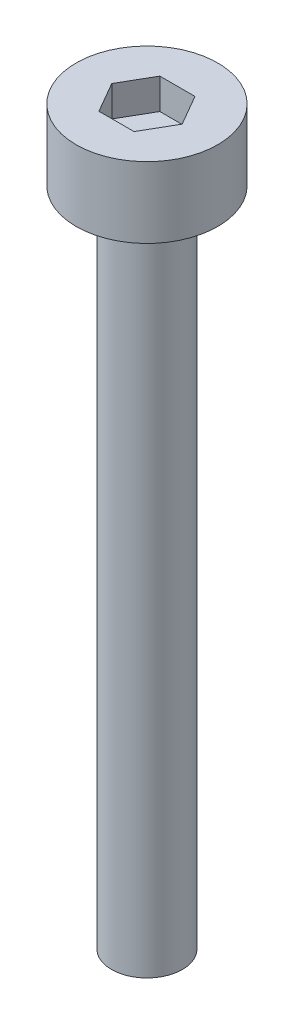
SolidWorks part; units mm, degrees
ref_plane "Front Plane" through (0, 0, 0) normal (0, 0, 1) x (1, 0, 0)
ref_plane "Top Plane" through (0, 0, 0) normal (0, 1, 0) x (1, 0, 0)
ref_plane "Right Plane" through (0, 0, 0) normal (1, 0, 0) x (0, 0, -1)
sketch "Sketch1" plane through (0, 0, 0) normal (0, 1, 0) x (1, 0, 0)
  circle A0 centre (0, 0) radius 1.5
  dimension "D1" = 3
extrude "ScrewShaft" add sketch "Sketch1" along normal blind 28
sketch "Sketch2" plane through (0, 28, 0) normal (0, 1, 0) x (1, 0, 0)
  circle A0 centre (0, 0) radius 3
  dimension "D1" = 6
extrude "Boss-Extrude2" add sketch "Sketch2" along normal blind 3
sketch "Sketch3" plane through (0, 31, 0) normal (0, 1, 0) x (1, 0, 0)
  line L0 (0, 0) -> (0, 1.29) construction
  line L1 (1.4896, 0) -> (0.7448, 1.29)
  line L2 (0.7448, 1.29) -> (-0.7448, 1.29)
  line L3 (-0.7448, 1.29) -> (-1.4896, 0)
  line L4 (-1.4896, 0) -> (-0.7448, -1.29)
  line L5 (-0.7448, -1.29) -> (0.7448, -1.29)
  line L6 (0.7448, -1.29) -> (1.4896, 0)
  circle A0 centre (0, 0) radius 1.29 construction
  dimension "D1" = 2.58
extrude "Cut-Extrude1" cut sketch "Sketch3" against normal blind 1.3
equation "\"X-ROD-SPACING\"=45"
equation "\"Y-ROD-SPACING\"=75"
equation "\"Z-ROD-SPACING\"=17.5"
equation "\"Y-BED-OFFSET\"=2"
equation "\"Y-BED-ROD-INSET\"=3.5"
equation "\"T-SLOT-NUT-FILLET-RADIUS\"=0.5"
equation "\"T-SLOT-SCREW-SHAFT-RADIUS\"=1.55"
equation "\"T-SLOT-SCREW-SHAFT-CUTOUT-LENGTH\"=11"
equation "\"T-SLOT-NUT-DEPTH\"=3.5"
equation "\"T-SLOT-NUT-WIDTH\"=2.85"
equation "\"T-SLOT-NUT-END-DISTANCE\"=8"
equation "\"ACRYLIC-THICKNESS\"=10"
equation "\"ACRYLIC-THICKNESS2\"=4.5"
equation "\"ACRYLIC-TAB-CUTOUT-SIZE\"=\"ACRYLIC-THICKNESS\"+\"ACRYLIC-TAB-TOLERANCE\"*2"
equation "\"ACRYLIC-TAB-WIDTH\"=\"ACRYLIC-THICKNESS\""
equation "\"ACRYLIC-M3-HOLE\"=2.9"
equation "\"SMOOTHROD-CAP-SCREW-DISTANCE\"=20"
equation "\"FRAME-WIDTH-INNER\"=370"
equation "\"NEMA17-HOLE-SPACING\"=31"
equation "\"NEMA17-CENTRAL-CUTOUT\"=22.5"
equation "\"Z-BRACKET-REACH\"=57"
equation "\"TOP-BRACKET-SPACING\"=40"
equation "\"SMOOTHROD-X-LENGTH\"=350"
equation "\"SMOOTHROD-Y-LENGTH\"=350"
equation "\"SMOOTHROD-Z-LENGTH\"=350"
equation "\"SMOOTHROD-TIGHTENING-HEADROOM\"=.25"
equation "\"LEADSCREW-Z-LENGTH\"=300"
equation "\"SCREW-LENGTH-FRAME\"=\"ACRYLIC-THICKNESS\" + 10"
equation "\"SCREW-HEAD-RADIUS\"=6"
equation "\"PRINTED-X-SMOOTHROD-DIAMETER\"=8.8"
equation "\"PRINTED-X-SMOOTHROD-CUTOUT\"=10"
equation "\"PRINTED-X-BASE-HEIGHT\"=10"
equation "\"PRINTED-LM8UU-CUTOUT-SIZE\"=15.5"
equation "\"PRINTED-LM8UU-CUTOUT-LENGTH\"=24.5"
equation "\"PRINTED-X-IDLER-HEIGHT\"=16"
equation "\"PSU-MOUNTING-WIDTH\"=50"
equation "\"PSU-MOUNTING-HEIGHT\"=150"
equation "\"D1@ScrewShaft\"=\"SCREW-LENGTH-EXTRUDER\""
equation "\"D1@Sketch2\"=\"SCREW-HEAD-RADIUS\""
equation "\"Y-BED-SCREW-SPACING\"=209"
equation "\"Y-BED-SCREW-CUTOUT-SLOT-HEIGHT\"=2.5"
equation "\"Z-ROD-INSET\"=13.5"
equation "\"SCREW-LENGTH-MOTOR\"=\"ACRYLIC-THICKNESS\" + 5"
equation "\"SCREW-LENGTH-EXTRUDER\"=28"
equation "\"Y-BELT-TO-ROD-DISTANCE\"=20"
equation "\"SPOOL-HOLDER-ROD-SPACING\"=150"
equation "\"ACRYLIC-X-CARRIAGE-WIDTH\"=55"
equation "\"ACRYLIC-X-CARRIAGE-HEIGHT\"=75"
equation "\"ACRYLIC-X-CARRIAGE-CENTER-TAB-SPACING\"=14"
